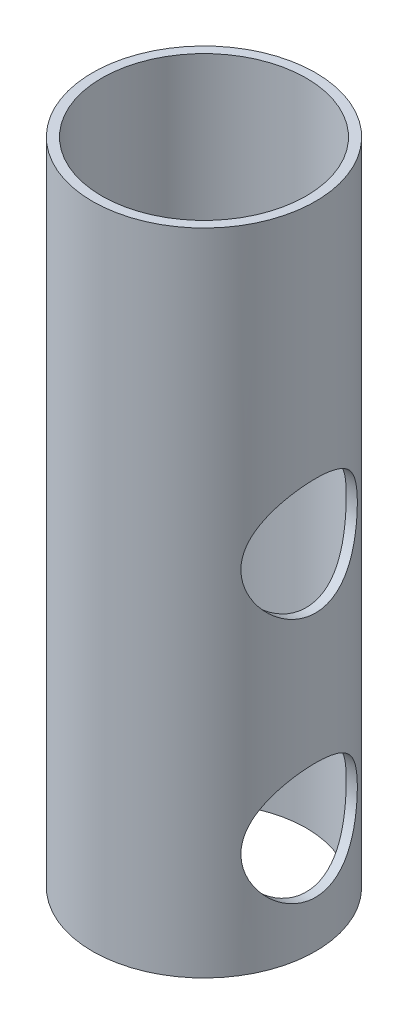
SolidWorks part; units mm, degrees
material "PTFE (general)"
ref_plane "Front Plane" through (0, 0, 0) normal (0, 0, 1) x (1, 0, 0)
ref_plane "Top Plane" through (0, 0, 0) normal (0, 1, 0) x (1, 0, 0)
ref_plane "Right Plane" through (0, 0, 0) normal (1, 0, 0) x (0, 0, -1)
sketch "Sketch1" plane through (0, 0, 0) normal (0, 1, 0) x (1, 0, 0)
  circle A0 centre (0, 0) radius 24
  circle A1 centre (0, 0) radius 22
  dimension "D1" = 2
  dimension "D2" = 44
extrude "Boss-Extrude1" add sketch "Sketch1" along normal blind 139.8
sketch "Sketch2" plane through (0, 0, 0) normal (1, 0, 0) x (0, 0, -1)
  line L1 (24, 139.8) -> (-24, 139.8) construction
  circle A0 centre (0, 22.6) radius 12.53
  circle A1 centre (0, 75.6) radius 12.53
  dimension "D2" = 25.06
  dimension "D3" = 25.06
  dimension "D1" = 64.2
  dimension "D5" = 53
extrude "Cut-Extrude1" cut sketch "Sketch2" along normal through all
